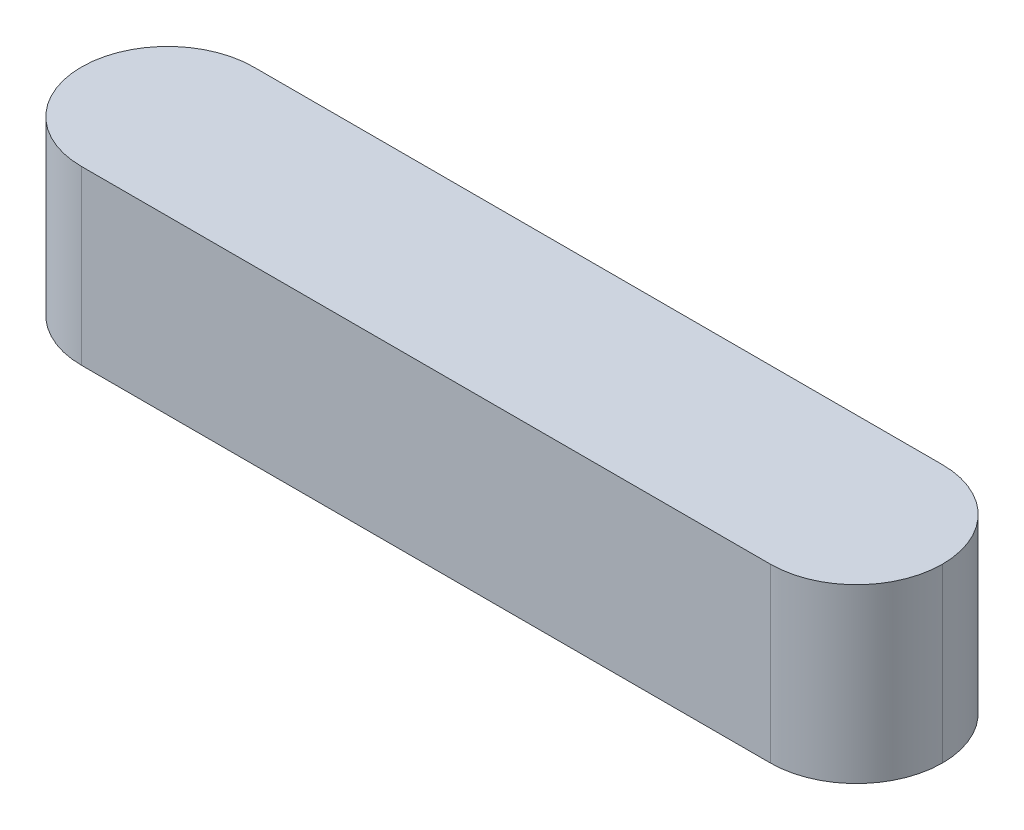
SolidWorks part; units mm, degrees
material "Cast Alloy Steel"
ref_plane "Front Plane" through (0, 0, 0) normal (0, 0, 1) x (1, 0, 0)
ref_plane "Top Plane" through (0, 0, 0) normal (0, 1, 0) x (1, 0, 0)
ref_plane "Right Plane" through (0, 0, 0) normal (1, 0, 0) x (0, 0, -1)
sketch "Sketch1" plane through (0, 0, 0) normal (0, 1, 0) x (1, 0, 0)
  line L1 (0, 0) -> (20, 0)
  line L2 (0, 0) -> (0, 4)
  line L3 (0, 4) -> (20, 4)
  line L4 (20, 0) -> (20, 4)
  dimension "D1" = 4
  dimension "D2" = 20
extrude "Extrude1" add sketch "Sketch1" along normal blind 4
fillet "Fillet1" radius 2 4 edges at (0, 2, -4) (0, 2, 0) (20, 2, -4) (20, 2, 0)
